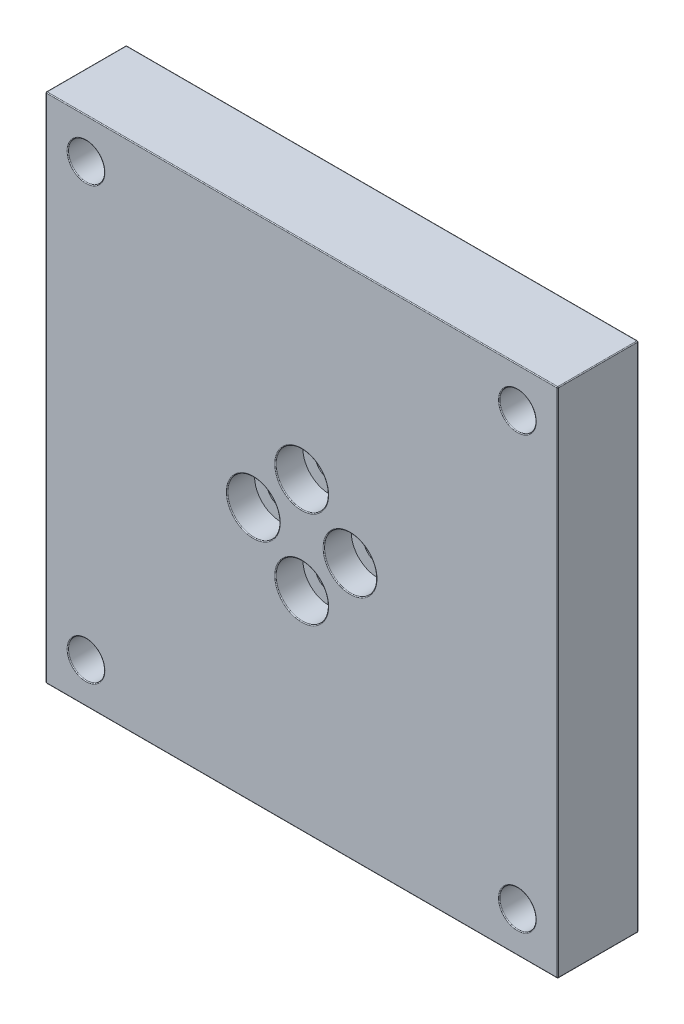
SolidWorks part; units mm, degrees
material "Сплав 2024"
ref_plane "Спереди" through (0, 0, 0) normal (0, 0, 1) x (1, 0, 0)
ref_plane "Сверху" through (0, 0, 0) normal (0, 1, 0) x (1, 0, 0)
ref_plane "Справа" through (0, 0, 0) normal (1, 0, 0) x (0, 0, -1)
sketch "Эскиз1" plane through (0, 0, 0) normal (0, 0, 1) x (1, 0, 0)
  line L1 (-31.75, 31.75) -> (31.75, 31.75)
  line L2 (-31.75, 31.75) -> (-31.75, -31.75)
  line L3 (-31.75, -31.75) -> (31.75, -31.75)
  line L4 (31.75, 31.75) -> (31.75, -31.75)
  line L5 (-31.75, 31.75) -> (31.75, -31.75) construction
  line L6 (-31.75, -31.75) -> (31.75, 31.75) construction
  point P0 (0, 0)
  dimension "D1" = 63.5
  dimension "D2" = 63.5
extrude "Бобышка-Вытянуть1" add sketch "Эскиз1" along normal blind 10
sketch "Эскиз2" plane through (0, 0, 10) normal (0, 0, 1) x (1, 0, 0)
  line L0 (-26.75, 31.75) -> (-26.75, -31.75) construction
  line L1 (31.75, 31.75) -> (-31.75, 31.75) construction
  line L2 (-31.75, -31.75) -> (31.75, -31.75) construction
  line L3 (26.75, 31.75) -> (26.75, -31.75) construction
  line L4 (-31.75, 26.75) -> (31.75, 26.75) construction
  line L5 (-31.75, 31.75) -> (-31.75, -31.75) construction
  line L6 (31.75, -31.75) -> (31.75, 31.75) construction
  line L7 (31.75, -26.75) -> (-31.75, -26.75) construction
  line L8 (0, 31.75) -> (0, -31.75) construction
  line L9 (-31.75, 0) -> (31.75, 0) construction
  circle A0 centre (0, 0) radius 6 construction
  dimension "D5" = 12
  dimension "D1" = 5
  dimension "D2" = 5
  dimension "D3" = 5
  dimension "D4" = 5
hole_wizard "Цековка для винта с внутренним шестигранником M31" positions "Эскиз4" profile "Эскиз3" counterbore size "M3" standard "Din" end condition through all
sketch "Эскиз4" plane through (0, 0, 10) normal (0, 0, 1) x (1, 0, 0)
  line L0 (0, 31.75) -> (0, -31.75) construction
  line L1 (-31.75, 0) -> (31.75, 0) construction
  circle A0 centre (0, 0) radius 6 construction
  point P0 (0, 6)
  point P6 (-6, 0)
  point P10 (0, -6)
  point P12 (6, 0)
sketch "Эскиз3" plane through (0, 6, 10) normal (1, 0, 0) x (0, -1, 0)
  line L0 (0, 0) -> (0, 10)
  line L1 (0, 10) -> (1.7, 10)
  line L3 (1.7, 10) -> (1.7, 3.4)
  line L4 (1.7, 3.4) -> (3.25, 3.4)
  line L5 (3.25, 3.4) -> (3.25, 0)
  line L7 (3.25, 0) -> (0, 0)
  line L11 (0, -6.35) -> (0, 107.95) construction
  dimension "Диаметр сквозного отверстия" = 3.4
  dimension "Глубина сквозного отверстия" = 10
  dimension "Диаметр цековки" = 6.5
  dimension "Глубина цековки" = 3.4
hole_wizard "Цековка для винта с внутренним шестигранником M41" positions "Эскиз6" profile "Эскиз5" counterbore size "M4" standard "Din" end condition through all
sketch "Эскиз6" plane through (0, 0, 0) normal (0, 0, -1) x (-1, 0, 0)
  line L0 (-26.75, 31.75) -> (-26.75, -31.75) construction
  line L1 (31.75, 26.75) -> (-31.75, 26.75) construction
  line L2 (-31.75, -26.75) -> (31.75, -26.75) construction
  line L3 (26.75, 31.75) -> (26.75, -31.75) construction
  point P0 (-26.75, 26.75)
  point P6 (-26.75, -26.75)
  point P10 (26.75, -26.75)
  point P14 (26.75, 26.75)
sketch "Эскиз5" plane through (26.75, 26.75, 0) normal (1, 0, 0) x (0, 1, 0)
  line L0 (0, 0) -> (0, 10)
  line L1 (0, 10) -> (2.25, 10)
  line L3 (2.25, 10) -> (2.25, 4.4)
  line L4 (2.25, 4.4) -> (4, 4.4)
  line L5 (4, 4.4) -> (4, 0)
  line L7 (4, 0) -> (0, 0)
  line L11 (0, -6.35) -> (0, 107.95) construction
  dimension "Диаметр сквозного отверстия" = 4.5
  dimension "Глубина сквозного отверстия" = 10
  dimension "Диаметр цековки" = 8
  dimension "Глубина цековки" = 4.4
sketch "Эскиз8" plane through (0, 0, 0) normal (0, 0, -1) x (-1, 0, 0)
  line L8 (-28.75, 28.75) -> (-28.75, -28.75)
  line L9 (28.75, 28.75) -> (-28.75, 28.75)
  line L10 (28.75, -28.75) -> (28.75, 28.75)
  line L11 (-28.75, -28.75) -> (28.75, -28.75)
  line L12 (-28.75, 16.8001) -> (-28.75, -16.8001)
  line L13 (16.8001, 28.75) -> (-16.8001, 28.75)
  line L14 (28.75, -16.8001) -> (28.75, 16.8001)
  line L15 (-16.8001, -28.75) -> (16.8001, -28.75)
  circle A31 centre (-26.75, 26.75) radius 7
  arc A32 (-26.05, 19.7851) -> (-19.7851, 26.05) centre (-26.75, 26.75) ccw
  circle A34 centre (26.75, 26.75) radius 7
  arc A35 (19.7851, 26.05) -> (26.05, 19.7851) centre (26.75, 26.75) ccw
  circle A37 centre (26.75, -26.75) radius 7
  arc A38 (26.05, -19.7851) -> (19.7851, -26.05) centre (26.75, -26.75) ccw
  arc A39 (-28.75, 16.8001) -> (-26.05, 19.7851) centre (-25.75, 16.8001) cw
  circle A40 centre (-26.75, -26.75) radius 7
  arc A41 (-19.7851, -26.05) -> (-26.05, -19.7851) centre (-26.75, -26.75) ccw
  arc A42 (-26.05, -19.7851) -> (-28.75, -16.8001) centre (-25.75, -16.8001) cw
  arc A43 (-16.8001, -28.75) -> (-19.7851, -26.05) centre (-16.8001, -25.75) cw
  arc A44 (19.7851, -26.05) -> (16.8001, -28.75) centre (16.8001, -25.75) cw
  arc A45 (28.75, -16.8001) -> (26.05, -19.7851) centre (25.75, -16.8001) cw
  arc A46 (26.05, 19.7851) -> (28.75, 16.8001) centre (25.75, 16.8001) cw
  arc A47 (16.8001, 28.75) -> (19.7851, 26.05) centre (16.8001, 25.75) cw
  arc A48 (-19.7851, 26.05) -> (-16.8001, 28.75) centre (-16.8001, 25.75) cw
  circle A49 centre (0, 0) radius 12.5
  dimension "D6" = 3
  dimension "D7" = 3
  dimension "D8" = 25
  dimension "D1" = 3
  dimension "D2" = 3
  dimension "D3" = 3
  dimension "D4" = 3
  dimension "D5" = 3
extrude "Вырез-Вытянуть1" cut sketch "Эскиз8" against normal offset from surface (7 mm away) 3 up to face at (24.5, 26.75, 10)
sketch "Эскиз9" plane through (0, 0, 7) normal (0, 0, -1) x (-1, 0, 0)
  line L0 (-26.75, 26.75) -> (26.75, -26.75) construction
  line L1 (26.75, 26.75) -> (-26.75, -26.75) construction
  line L2 (20.8546, 22.9759) -> (7.7143, 9.8356)
  line L3 (-22.9759, 20.8546) -> (-9.8356, 7.7143)
  line L4 (22.9759, 20.8546) -> (9.8356, 7.7143)
  line L5 (-20.8546, 22.9759) -> (-7.7143, 9.8356)
  line L8 (-25.6893, 27.8107) -> (27.8107, -25.6893) construction
  line L10 (-27.8107, 25.6893) -> (25.6893, -27.8107) construction
  line L12 (27.8107, 25.6893) -> (-25.6893, -27.8107) construction
  line L13 (7.7143, -9.8356) -> (20.8546, -22.9759)
  line L14 (25.6893, 27.8107) -> (-27.8107, -25.6893) construction
  line L15 (9.8356, -7.7143) -> (22.9759, -20.8546)
  line L16 (-7.7143, -9.8356) -> (-20.8546, -22.9759)
  line L17 (-9.8356, -7.7143) -> (-22.9759, -20.8546)
  circle A0 centre (0, 0) radius 12.5 construction
  arc A1 (-7.7143, 9.8356) -> (-9.8356, 7.7143) centre (0, 0) ccw
  arc A2 (-26.05, 19.7851) -> (-19.7851, 26.05) centre (-26.75, 26.75) ccw construction
  arc A3 (19.7851, 26.05) -> (26.05, 19.7851) centre (26.75, 26.75) ccw construction
  arc A4 (26.05, -19.7851) -> (19.7851, -26.05) centre (26.75, -26.75) ccw construction
  arc A5 (-19.7851, -26.05) -> (-26.05, -19.7851) centre (-26.75, -26.75) ccw construction
  arc A6 (-22.9759, 20.8546) -> (-20.8546, 22.9759) centre (-26.75, 26.75) ccw
  arc A7 (20.8546, 22.9759) -> (22.9759, 20.8546) centre (26.75, 26.75) ccw
  arc A8 (22.9759, -20.8546) -> (20.8546, -22.9759) centre (26.75, -26.75) ccw
  arc A9 (-20.8546, -22.9759) -> (-22.9759, -20.8546) centre (-26.75, -26.75) ccw
  arc A10 (-9.8356, -7.7143) -> (-7.7143, -9.8356) centre (0, 0) ccw
  arc A11 (9.8356, 7.7143) -> (7.7143, 9.8356) centre (0, 0) ccw
  arc A12 (7.7143, -9.8356) -> (9.8356, -7.7143) centre (0, 0) ccw
  dimension "D1" = 1.5
  dimension "D2" = 1.5
extrude "Бобышка-Вытянуть2" add sketch "Эскиз9" along normal up to surface (7 mm away) up to face at (7.7, 0, 0)
fillet "Скругление1" radius 3 16 edges at (22.9759, 20.8546, 3.5) (9.8356, 7.7143, 3.5) (9.8356, -7.7143, 3.5) (22.9759, -20.8546, 3.5) (20.8546, -22.9759, 3.5) (7.7143, -9.8356, 3.5) (-7.7143, -9.8356, 3.5) (-20.8546, -22.9759, 3.5) (-22.9759, -20.8546, 3.5) (-9.8356, -7.7143, 3.5) (-9.8356, 7.7143, 3.5) (20.8546, 22.9759, 3.5) (7.7143, 9.8356, 3.5) (-7.7143, 9.8356, 3.5) (-22.9759, 20.8546, 3.5) (-20.8546, 22.9759, 3.5)
fillet "Скругление2" radius 0.1 76 edges at (31.75, -31.75, 5) (-31.75, -31.75, 5) (31.75, 31.75, 5) (-31.75, 31.75, 5) (1.7, 6, 0) (-4.3, 0, 0) (1.7, -6, 0) (7.7, 0, 0) (0, 31.75, 0) (-31.75, 0, 0) (0, -31.75, 0) (31.75, 0, 0) (-30.75, 26.75, 0) (-30.75, -26.75, 0) (22.75, -26.75, 0) (22.75, 26.75, 0) (-20.172, 22.9235, 0) (-19.9029, 25.2949, 0) (-18.8126, 27.9749, 0) (0, 28.75, 0) (18.8126, 27.9749, 0) (19.9029, 25.2949, 0) (20.172, 22.9235, 0) (14.4011, 16.5224, 0) (7.7464, 10.7025, 0) (0, 12.5, 0) (-7.7464, 10.7025, 0) (-14.4011, 16.5224, 0) (20.172, -22.9235, 0) (19.9029, -25.2949, 0) (18.8126, -27.9749, 0) (0, -28.75, 0) (-18.8126, -27.9749, 0) (-19.9029, -25.2949, 0) (-20.172, -22.9235, 0) (-14.4011, -16.5224, 0) (-7.7464, -10.7025, 0) (0, -12.5, 0) (7.7464, -10.7025, 0) (14.4011, -16.5224, 0) (22.9235, 20.172, 0) (25.2949, 19.9029, 0) (27.9749, 18.8126, 0) (28.75, 0, 0) (27.9749, -18.8126, 0) (25.2949, -19.9029, 0) (22.9235, -20.172, 0) (16.5224, -14.4011, 0) (10.7025, -7.7464, 0) (12.5, 0, 0) (10.7025, 7.7464, 0) (16.5224, 14.4011, 0) (-22.9235, -20.172, 0) (-25.2949, -19.9029, 0) (-27.9749, -18.8126, 0) (-28.75, 0, 0) (-27.9749, 18.8126, 0) (-25.2949, 19.9029, 0) (-22.9235, 20.172, 0) (-16.5224, 14.4011, 0) (-10.7025, 7.7464, 0) (-12.5, 0, 0) (-10.7025, -7.7464, 0) (-16.5224, -14.4011, 0) (0, -31.75, 10) (-31.75, 0, 10) (0, 31.75, 10) (31.75, 0, 10) (9.25, 0, 10) (3.25, -6, 10) (-2.75, 0, 10) (3.25, 6, 10) (-29, 26.75, 10) (-29, -26.75, 10) (24.5, -26.75, 10) (24.5, 26.75, 10)
